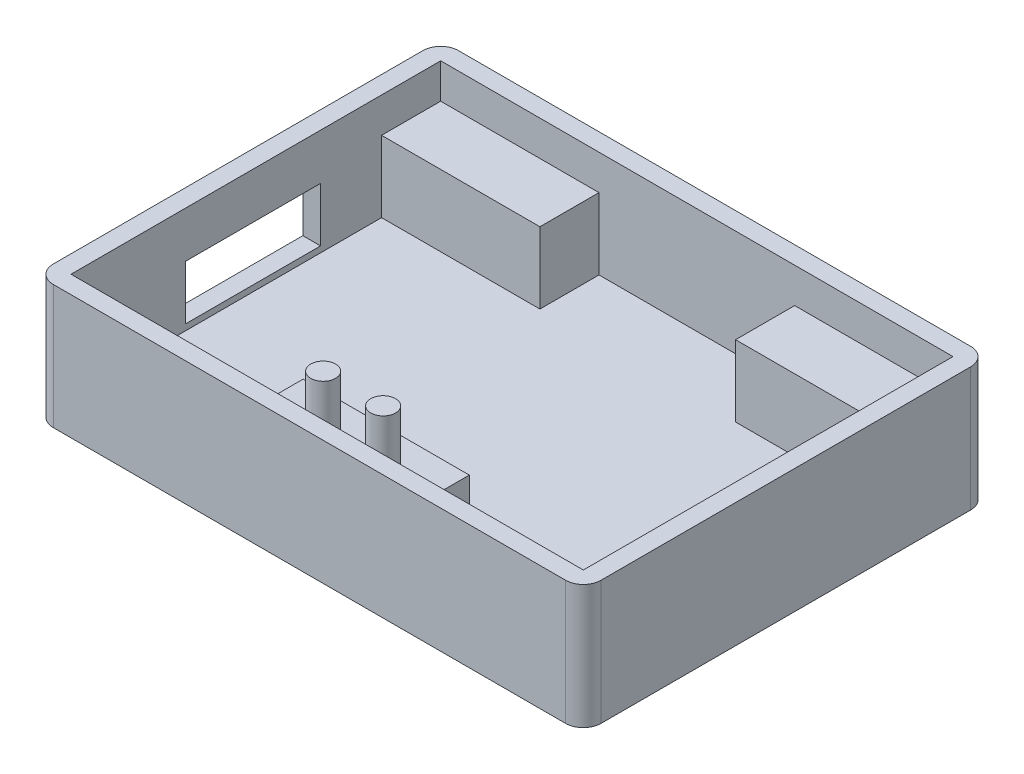
SolidWorks part; units mm, degrees
note: The reader was unsure of these and kept them because the rebuilt part matched: shared geometry of "Sketch1<14>", "Sketch1<15>", "Sketch1<16>".
ref_plane "Front Plane" through (0, 0, 0) normal (0, 0, 1) x (1, 0, 0)
ref_plane "Top Plane" through (0, 0, 0) normal (0, 1, 0) x (1, 0, 0)
ref_plane "Right Plane" through (0, 0, 0) normal (1, 0, 0) x (0, 0, -1)
sketch "Sketch1" plane through (0, 0, 0) normal (0, 1, 0) x (1, 0, 0)
  line L36 (36.6269, 26.2547) -> (-36.8231, 26.2547)
  line L37 (-36.8231, 26.2547) -> (-36.8231, -26.7453)
  line L38 (-36.8231, -26.7453) -> (36.6269, -26.7453)
  line L39 (36.6269, -26.7453) -> (36.6269, 26.2547)
  line L40 (39.1669, 28.7947) -> (-39.3631, 28.7947)
  line L41 (-39.3631, 28.7947) -> (-39.3631, -29.2853)
  line L42 (-39.3631, -29.2853) -> (39.1669, -29.2853)
  line L43 (39.1669, -29.2853) -> (39.1669, 28.7947)
  line L49 (-36.8231, 26.2547) -> (-14.1241, 26.2547)
  line L50 (-36.8231, 26.2547) -> (-36.8231, 17.782)
  line L51 (-36.8231, 17.782) -> (-14.1241, 17.782)
  line L52 (-14.1241, 26.2547) -> (-14.1241, 17.782)
  line L53 (36.6269, 26.2547) -> (13.9279, 26.2547)
  line L54 (36.6269, 26.2547) -> (36.6269, 17.782)
  line L55 (36.6269, 17.782) -> (13.9279, 17.782)
  line L56 (13.9279, 26.2547) -> (13.9279, 17.782)
  line L57 (-12.1762, -26.7453) -> (11.6491, -26.7453)
  line L58 (-12.1762, -26.7453) -> (-12.1762, -18.1142)
  line L59 (-12.1762, -18.1142) -> (11.6491, -18.1142)
  line L60 (11.6491, -26.7453) -> (11.6491, -18.1142)
  circle A14 centre (-4.1712, -23.2472) radius 1.778
  circle A15 centre (4.4288, -23.2472) radius 1.778
  dimension "D1" = 2.54
  dimension "D2" = 3.556
extrude "Boss-Extrude5" add sketch "Sketch1" along normal blind 2.54 contours L38 L39 L36 L37 A15 A14
extrude "Boss-Extrude6" add sketch "Sketch1<14>" along normal blind 17.78 contours L42 L43 L40 L41 L39 L38 L37 L36
sketch "Sketch1<14>" plane through (0, 0, 0) normal (0, 1, 0) x (1, 0, 0) same geometry as "Sketch1"
extrude "Boss-Extrude7" add sketch "Sketch1<15>" along normal blind 20.32 contours A14 | A15
sketch "Sketch1<15>" plane through (0, 0, 0) normal (0, 1, 0) x (1, 0, 0) same geometry as "Sketch1"
extrude "Boss-Extrude8" add sketch "Sketch1<16>" along normal blind 12.7635 contours L38 L60 L59 L58 A15 A14 | L52 L36 L37 L51 | L36 L56 L55 L39
sketch "Sketch1<16>" plane through (0, 0, 0) normal (0, 1, 0) x (1, 0, 0) same geometry as "Sketch1"
sketch "Sketch2" plane through (-39.3631, 0, 0) normal (-1, 0, 0) x (0, 0, 1)
  line L1 (-9.0328, 3.4082) -> (10.314, 3.4082)
  line L2 (-9.0328, 3.4082) -> (-9.0328, 11.1724)
  line L3 (-9.0328, 11.1724) -> (10.314, 11.1724)
  line L4 (10.314, 3.4082) -> (10.314, 11.1724)
extrude "Cut-Extrude1" cut sketch "Sketch2" against normal blind 2.54 contours L1 L4 L3 L2
fillet "Fillet1" radius 2.54 4 edges at (39.1669, 8.89, -28.7947) (-39.3631, 8.89, -28.7947) (-39.3631, 8.89, 29.2853) (39.1669, 8.89, 29.2853)
